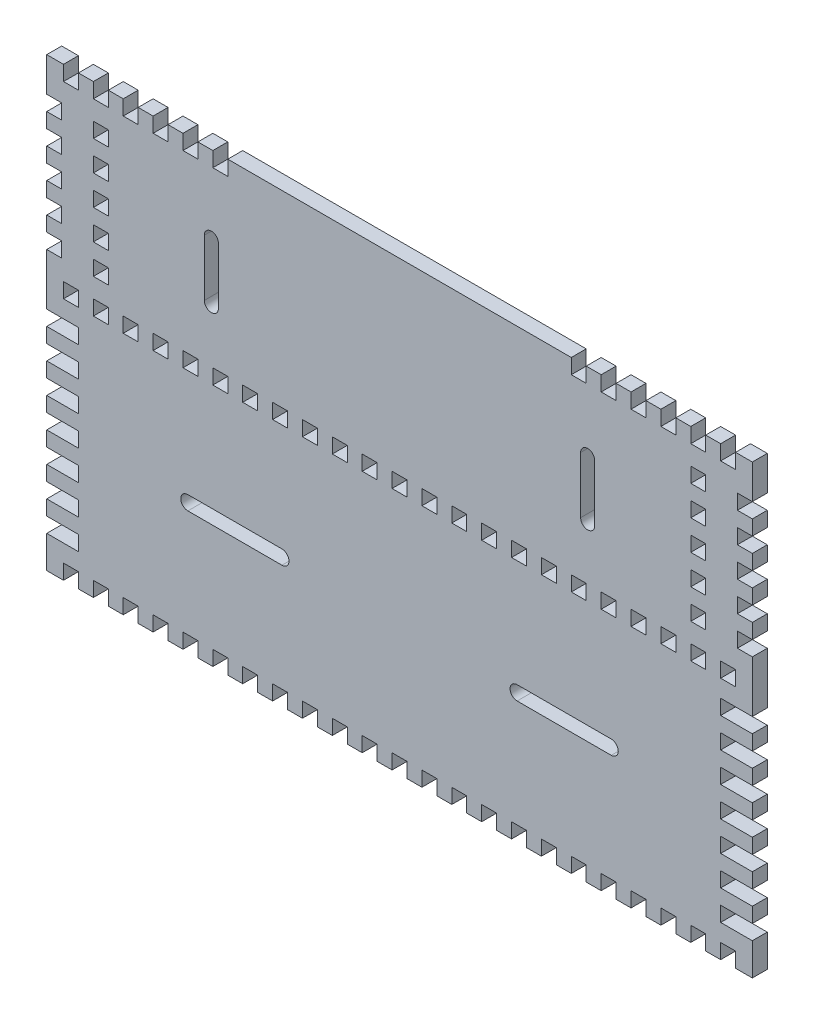
SolidWorks part; units mm, degrees
ref_plane "Front Plane" through (0, 0, 0) normal (0, 0, 1) x (1, 0, 0)
ref_plane "Top Plane" through (0, 0, 0) normal (0, 1, 0) x (1, 0, 0)
ref_plane "Right Plane" through (0, 0, 0) normal (1, 0, 0) x (0, 0, -1)
sketch "Sketch1" plane through (0, 0, 0) normal (0, 0, 1) x (1, 0, 0)
  line L1 (75, -27.5) -> (-75, -27.5)
  line L2 (75, -27.5) -> (75, 27.5)
  line L3 (75, 27.5) -> (-75, 27.5)
  line L4 (-75, -27.5) -> (-75, 27.5)
  line L5 (75, -27.5) -> (-75, 27.5) construction
  line L6 (75, 27.5) -> (-75, -27.5) construction
  point P0 (0, 0)
  dimension "D1" = 150
  dimension "D2" = 55
extrude "Boss-Extrude1" add sketch "Sketch1" along normal blind 3.175
sketch "Sketch2" plane through (0, 0, 0) normal (0, 0, -1) x (-1, 0, 0)
  line L0 (-75, 27.5) -> (75, 27.5) construction
  line L1 (-1.5875, 30.675) -> (1.5875, 30.675)
  line L2 (-1.5875, 30.675) -> (-1.5875, 24.325)
  line L3 (-1.5875, 24.325) -> (1.5875, 24.325)
  line L4 (1.5875, 30.675) -> (1.5875, 24.325)
  line L5 (-1.5875, 30.675) -> (1.5875, 24.325) construction
  line L6 (-1.5875, 24.325) -> (1.5875, 30.675) construction
  point P0 (0, 27.5)
  dimension "D1" = 3.175
  dimension "D2" = 6.35
extrude "Cut-Extrude1" cut sketch "Sketch2" against normal up to next
pattern_linear "LPattern1" count 12 spacing 6.35 along (1, 0, 0) count 12 spacing 6.35 along (-1, 0, 0) of "Cut-Extrude1"
mirror "Mirror1" about plane through (0, 0, 0) normal (0, 1, 0) of "LPattern1", "Cut-Extrude1"
sketch "Sketch3" plane through (0, 0, 0) normal (0, 0, -1) x (-1, 0, 0)
  line L0 (40, 0) -> (-40, 0) construction
  circle A0 centre (-40, 0) radius 1.5
  circle A1 centre (40, 0) radius 1.5
  point P4 (0, 0)
  dimension "D2" = 3
  dimension "D1" = 80
extrude "Cut-Extrude2" [suppressed] cut sketch "Sketch3" against normal blind 10
sketch "Sketch5" plane through (0, 0, 3.175) normal (0, 0, 1) x (1, 0, 0)
  line L0 (-75, 27.5) -> (-75, -27.5) construction
  line L1 (-78.175, 1.5875) -> (-71.825, 1.5875)
  line L2 (-78.175, 1.5875) -> (-78.175, -1.5875)
  line L3 (-78.175, -1.5875) -> (-71.825, -1.5875)
  line L4 (-71.825, 1.5875) -> (-71.825, -1.5875)
  line L5 (-78.175, 1.5875) -> (-71.825, -1.5875) construction
  line L6 (-78.175, -1.5875) -> (-71.825, 1.5875) construction
  point P0 (-75, 0)
  dimension "D1" = 6.35
  dimension "D2" = 3.175
extrude "Cut-Extrude3" cut sketch "Sketch5" against normal blind 10
pattern_linear "LPattern2" count 4 spacing 6.35 along (0, 1, 0) count 4 spacing 6.35 along (0, -1, 0) of "Cut-Extrude3"
mirror "Mirror2" about plane through (0, 0, 0) normal (1, 0, 0) of "LPattern2", "Cut-Extrude3"
sketch "Sketch7" plane through (0, 0, 0) normal (0, 0, -1) x (-1, 0, 0)
  line L1 (-71.825, 20.6375) -> (-68.65, 20.6375)
  line L2 (-71.825, 20.6375) -> (-71.825, 17.4625)
  line L3 (-71.825, 17.4625) -> (-68.65, 17.4625)
  line L4 (-68.65, 20.6375) -> (-68.65, 17.4625)
  dimension "D1" = 3.175
extrude "Cut-Extrude5" cut sketch "Sketch7" against normal blind 10
pattern_linear "LPattern4" count 7 spacing 6.35 along (0, -1, 0) of "Cut-Extrude5"
mirror "Mirror3" about plane through (0, 0, 0) normal (1, 0, 0) of "LPattern4", "Cut-Extrude5"
sketch "Sketch8" plane through (0, 0, 0) normal (0, 0, -1) x (-1, 0, 0)
  line L0 (35, 0) -> (-35, 0) construction
  line L1 (-25, 0) -> (-45, 0) construction
  line L2 (-25, -1.5) -> (-45, -1.5)
  line L3 (-25, 1.5) -> (-45, 1.5)
  line L4 (45, 0) -> (25, 0) construction
  line L5 (45, -1.5) -> (25, -1.5)
  line L6 (45, 1.5) -> (25, 1.5)
  arc A0 (-25, -1.5) -> (-25, 1.5) centre (-25, 0) ccw
  arc A1 (-45, 1.5) -> (-45, -1.5) centre (-45, 0) ccw
  arc A2 (45, -1.5) -> (45, 1.5) centre (45, 0) ccw
  arc A3 (25, 1.5) -> (25, -1.5) centre (25, 0) ccw
  point P4 (0, 0)
  point P7 (-35, 0)
  point P14 (35, 0)
  dimension "D1" = 70
  dimension "D2" = 3
  dimension "D3" = 20
  dimension "D4" = 20
  dimension "D5" = 3
extrude "Cut-Extrude6" cut sketch "Sketch8" against normal blind 10
sketch "Sketch9" plane through (0, 0, 0) normal (0, 0, -1) x (-1, 0, 0)
  line L1 (-75, 27.5) -> (75, 27.5)
  line L2 (-75, 27.5) -> (-75, 67.5)
  line L3 (-75, 67.5) -> (75, 67.5)
  line L4 (75, 27.5) -> (75, 67.5)
  dimension "D1" = 40
extrude "Boss-Extrude2" add sketch "Sketch9" against normal up to surface (3.175 mm away) up to face at (35, 0, 3.175)
sketch "Sketch10" plane through (0, 0, 0) normal (0, 0, -1) x (-1, 0, 0)
  line L0 (-40, 48.8996) -> (40, 48.8996) construction
  line L1 (-38.5, 48.8996) -> (-41.5, 48.8996) construction
  line L2 (-38.5, 47.3996) -> (-41.5, 47.3996)
  line L3 (-38.5, 50.3996) -> (-41.5, 50.3996)
  line L4 (38.5, 48.8996) -> (41.5, 48.8996) construction
  line L5 (38.5, 50.3996) -> (41.5, 50.3996)
  line L6 (38.5, 47.3996) -> (41.5, 47.3996)
  arc A0 (-38.5, 47.3996) -> (-38.5, 50.3996) centre (-38.5, 48.8996) ccw
  arc A1 (-41.5, 50.3996) -> (-41.5, 47.3996) centre (-41.5, 48.8996) ccw
  arc A2 (38.5, 50.3996) -> (38.5, 47.3996) centre (38.5, 48.8996) ccw
  arc A3 (41.5, 47.3996) -> (41.5, 50.3996) centre (41.5, 48.8996) ccw
  point P3 (0, 48.8996)
  point P5 (-40, 48.8996)
  point P12 (40, 48.8996)
  dimension "D1" = 80
  dimension "D2" = 3
  dimension "D3" = 3
  dimension "D4" = 3
  dimension "D5" = 3
  dimension "D6" = 40
extrude "Cut-Extrude7" [suppressed] cut sketch "Sketch10" against normal blind 10
sketch "Sketch11" plane through (0, 0, 0) normal (0, 0, -1) x (-1, 0, 0)
  line L0 (75, 67.5) -> (-75, 67.5) construction
  line L1 (0, 67.5) -> (1.5875, 67.5)
  line L3 (0, 64.325) -> (1.5875, 64.325)
  line L4 (1.5875, 67.5) -> (1.5875, 64.325)
  line L6 (0, 64.325) -> (-1.5875, 64.325)
  line L8 (0, 67.5) -> (-1.5875, 67.5)
  line L9 (-1.5875, 64.325) -> (-1.5875, 67.5)
  dimension "D1" = 1.5875
  dimension "D2" = 3.175
  dimension "D3" = 1.5875
extrude "Cut-Extrude8" cut sketch "Sketch11" against normal blind 10
pattern_linear "LPattern5" count 12 spacing 6.35 along (1, 0, 0) count 12 spacing 6.35 along (-1, 0, 0) of "Cut-Extrude8"
sketch "Sketch12" plane through (0, 0, 0) normal (0, 0, -1) x (-1, 0, 0)
  line L1 (-36.5125, 67.5) -> (36.5125, 67.5)
  line L2 (-36.5125, 67.5) -> (-36.5125, 64.325)
  line L3 (-36.5125, 64.325) -> (36.5125, 64.325)
  line L4 (36.5125, 67.5) -> (36.5125, 64.325)
extrude "Boss-Extrude3" add sketch "Sketch12" against normal up to surface (3.175 mm away) up to face at (0, 15.4098, 3.175)
sketch "Sketch13" plane through (0, 0, 0) normal (0, 0, -1) x (-1, 0, 0)
  line L0 (-75, 67.5) -> (-75, 24.325) construction
  line L1 (-75, 20.6375) -> (-75, 67.5) construction
sketch "Sketch14" plane through (0, 0, 0) normal (0, 0, -1) x (-1, 0, 0)
  line L0 (-75, 67.5) -> (-75, 24.325) construction
  line L1 (-78.175, 47.5) -> (-71.825, 47.5)
  line L2 (-78.175, 47.5) -> (-78.175, 44.325)
  line L3 (-78.175, 44.325) -> (-71.825, 44.325)
  line L4 (-71.825, 47.5) -> (-71.825, 44.325)
  line L5 (-78.175, 47.5) -> (-71.825, 44.325) construction
  line L6 (-78.175, 44.325) -> (-71.825, 47.5) construction
  point P0 (-75, 45.9125)
  dimension "D1" = 3.175
  dimension "D2" = 6.35
extrude "Cut-Extrude9" cut sketch "Sketch14" against normal blind 10
pattern_linear "LPattern6" count 3 spacing 6.35 along (0, 1, 0) count 3 spacing 6.35 along (0, -1, 0) of "Cut-Extrude9"
mirror "Mirror4" about plane through (0, 0, 0) normal (1, 0, 0) of "LPattern6", "Cut-Extrude9"
sketch "Sketch15" plane through (0, 0, 0) normal (0, 0, -1) x (-1, 0, 0)
  line L1 (-65.0875, 47.5) -> (-61.9125, 47.5)
  line L2 (-65.0875, 47.5) -> (-65.0875, 44.325)
  line L3 (-65.0875, 44.325) -> (-61.9125, 44.325)
  line L4 (-61.9125, 47.5) -> (-61.9125, 44.325)
extrude "Cut-Extrude10" cut sketch "Sketch15" against normal blind 10
pattern_linear "LPattern7" count 3 spacing 6.35 along (0, 1, 0) count 3 spacing 6.35 along (0, -1, 0) of "Cut-Extrude10"
mirror "Mirror5" about plane through (0, 0, 0) normal (1, 0, 0) of "LPattern7", "Cut-Extrude10"
sketch "Sketch17" plane through (0, 0, 0) normal (0, 0, -1) x (-1, 0, 0)
  line L0 (-40, 51) -> (-40, 39) construction
  line L1 (-38.5, 51) -> (-38.5, 39)
  line L2 (-41.5, 51) -> (-41.5, 39)
  arc A0 (-38.5, 51) -> (-41.5, 51) centre (-40, 51) ccw
  arc A1 (-41.5, 39) -> (-38.5, 39) centre (-40, 39) ccw
  point P2 (-40, 45)
  dimension "D1" = 40
  dimension "D2" = 3
  dimension "D3" = 12
  dimension "D4" = 45
extrude "Cut-Extrude12" cut sketch "Sketch17" against normal blind 10
mirror "Mirror6" about plane through (0, 0, 0) normal (1, 0, 0) of "Cut-Extrude12"
sketch "Sketch19" plane through (0, 0, 0) normal (0, 0, -1) x (-1, 0, 0)
  line L1 (68.65, -20.6375) -> (68.2625, -20.6375)
  line L2 (68.65, -20.6375) -> (68.65, -17.4625)
  line L3 (68.65, -17.4625) -> (68.2625, -17.4625)
  line L4 (68.2625, -20.6375) -> (68.2625, -17.4625)
  line L5 (68.65, -14.2875) -> (68.2625, -14.2875)
  line L6 (68.65, -14.2875) -> (68.65, -11.1125)
  line L7 (68.65, -11.1125) -> (68.2625, -11.1125)
  line L8 (68.2625, -14.2875) -> (68.2625, -11.1125)
  line L9 (68.65, -4.7625) -> (68.2625, -4.7625)
  line L10 (68.65, -4.7625) -> (68.65, -7.9375)
  line L11 (68.65, -7.9375) -> (68.2625, -7.9375)
  line L12 (68.2625, -4.7625) -> (68.2625, -7.9375)
  line L13 (68.65, 1.5875) -> (68.2625, 1.5875)
  line L14 (68.65, 1.5875) -> (68.65, -1.5875)
  line L15 (68.65, -1.5875) -> (68.2625, -1.5875)
  line L16 (68.2625, 1.5875) -> (68.2625, -1.5875)
  line L17 (68.65, 7.9375) -> (68.2625, 7.9375)
  line L18 (68.65, 7.9375) -> (68.65, 4.7625)
  line L19 (68.65, 4.7625) -> (68.2625, 4.7625)
  line L20 (68.2625, 7.9375) -> (68.2625, 4.7625)
  line L21 (68.65, 14.2875) -> (68.2625, 14.2875)
  line L22 (68.65, 14.2875) -> (68.65, 11.1125)
  line L23 (68.65, 11.1125) -> (68.2625, 11.1125)
  line L24 (68.2625, 14.2875) -> (68.2625, 11.1125)
  line L25 (68.65, 20.6375) -> (68.2625, 20.6375)
  line L26 (68.65, 20.6375) -> (68.65, 17.4625)
  line L27 (68.65, 17.4625) -> (68.2625, 17.4625)
  line L28 (68.2625, 20.6375) -> (68.2625, 17.4625)
extrude "Cut-Extrude13" cut sketch "Sketch19" against normal blind 10
mirror "Mirror7" about plane through (0, 0, 0) normal (1, 0, 0) of "Cut-Extrude13"
